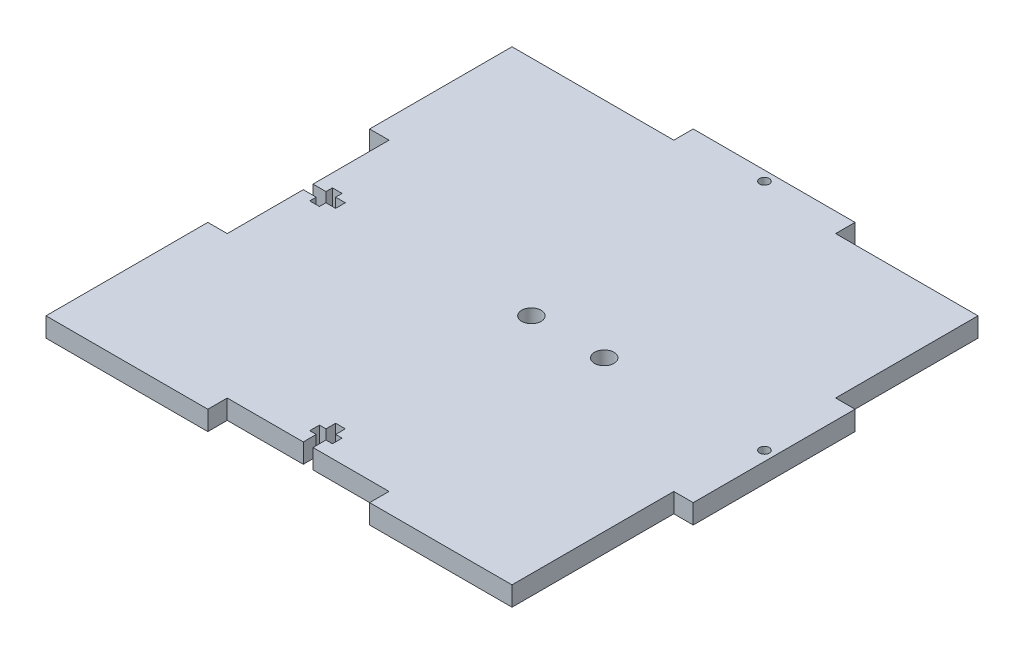
SolidWorks part; units mm, degrees
material "Acrylic (Medium-high impact)"
ref_plane "Front Plane" through (0, 0, 0) normal (0, 0, 1) x (1, 0, 0)
ref_plane "Top Plane" through (0, 0, 0) normal (0, 1, 0) x (1, 0, 0)
ref_plane "Right Plane" through (0, 0, 0) normal (1, 0, 0) x (0, 0, -1)
sketch "Sketch1" plane through (0, 0, 0) normal (0, 1, 0) x (1, 0, 0)
  line L0 (-72, 28) -> (-66, 28)
  line L1 (-72, -72) -> (72, -72)
  line L2 (-72, -72) -> (-72, 72)
  line L3 (-72, 72) -> (72, 72)
  line L4 (72, -72) -> (72, 72)
  line L5 (-72, -72) -> (72, 72) construction
  line L6 (-72, 72) -> (72, -72) construction
  line L7 (-66, 28) -> (-66, -22)
  line L8 (28, -72) -> (28, -66)
  line L9 (-22, 72) -> (-22, 78)
  line L10 (-22, 78) -> (28, 78)
  line L11 (28, 72) -> (28, 78)
  line L12 (72, 28) -> (78, 28)
  line L13 (78, 28) -> (78, -22)
  line L14 (-22, -72) -> (-22, -66)
  line L15 (-22, -66) -> (28, -66)
  line L16 (3, 78) -> (3, -72) construction
  line L17 (-72, 3) -> (78, 3) construction
  line L18 (72, -22) -> (78, -22)
  line L19 (-72, -22) -> (-66, -22)
  line L20 (75, 28) -> (75, -22) construction
  line L21 (4.5, -66) -> (4.5, -62)
  line L22 (4.5, -62) -> (6.5, -62)
  line L23 (6.5, -62) -> (6.5, -59)
  line L24 (6.5, -59) -> (4.5, -59)
  line L25 (4.5, -59) -> (4.5, -56)
  line L26 (4.5, -56) -> (1.5, -56)
  line L27 (1.5, -66) -> (1.5, -62)
  line L28 (1.5, -62) -> (-0.5, -62)
  line L29 (-0.5, -59) -> (1.5, -59)
  line L30 (-0.5, -62) -> (-0.5, -59)
  line L31 (1.5, -59) -> (1.5, -56)
  line L32 (-59, 4.5) -> (-56, 4.5)
  line L33 (-62, 4.5) -> (-62, 6.5)
  line L34 (-59, 6.5) -> (-59, 4.5)
  line L35 (-62, 6.5) -> (-59, 6.5)
  line L36 (-66, 4.5) -> (-62, 4.5)
  line L37 (-66, 1.5) -> (-62, 1.5)
  line L38 (-62, 1.5) -> (-62, -0.5)
  line L39 (-62, -0.5) -> (-59, -0.5)
  line L40 (-59, -0.5) -> (-59, 1.5)
  line L41 (-59, 1.5) -> (-56, 1.5)
  line L42 (-56, 4.5) -> (-56, 1.5)
  circle A0 centre (75, 3) radius 1.5
  circle A1 centre (3, 75) radius 1.5
  circle A2 centre (3, 3) radius 3
  circle A3 centre (25.5, 3) radius 3
  point P0 (0, 0)
  point P22 (3, 3)
  point P27 (3, 3)
  point P40 (3, -66)
  point P45 (-66, 3)
  point P49 (3, -56)
  dimension "D4" = 3
  dimension "D9" = 6
  dimension "D1" = 144
  dimension "D2" = 25
  dimension "D3" = 6
  dimension "D5" = 4
  dimension "D6" = 2
  dimension "D7" = 3
  dimension "D8" = 1.5
  dimension "D10" = 2
extrude "Boss-Extrude1" add sketch "Sketch1" along normal blind 6 contours L19 L2 L1 L14 L15 L8 L4 L3 L0 L7 | L3 L11 L10 L9 | L4 L18 L13 L12 region at (-69.9635, 0, -50) region at (-21.4964, 0, -75) region at (75, 0, -27.4964)
